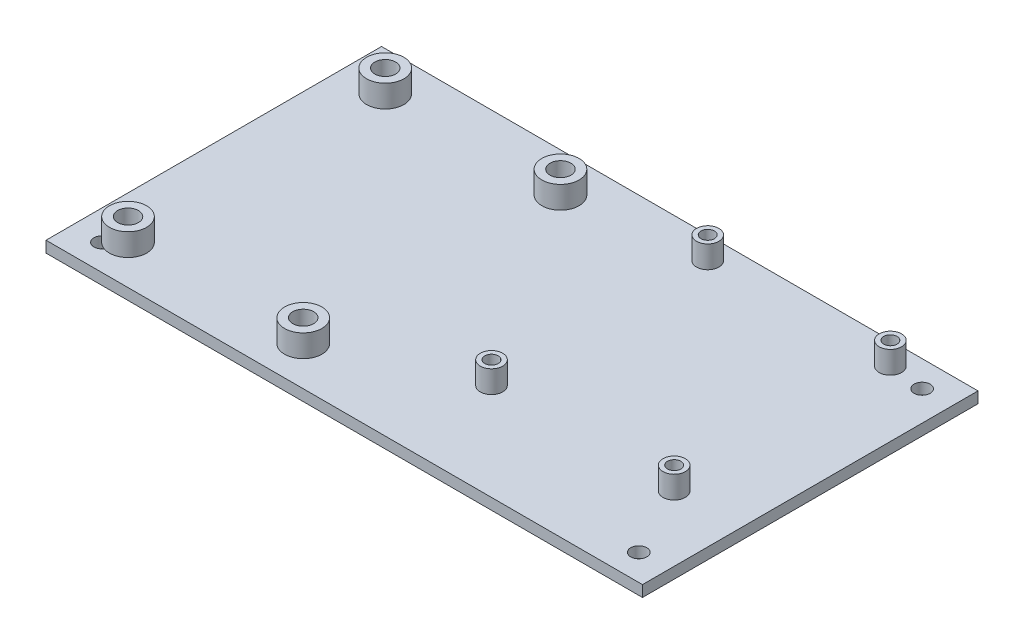
SolidWorks part; units mm, degrees
ref_plane "Front Plane" through (0, 0, 0) normal (0, 0, 1) x (1, 0, 0)
ref_plane "Top Plane" through (0, 0, 0) normal (0, 1, 0) x (1, 0, 0)
ref_plane "Right Plane" through (0, 0, 0) normal (1, 0, 0) x (0, 0, -1)
sketch "SK_Plate" plane through (0, 0, 0) normal (0, 1, 0) x (1, 0, 0)
  line L1 (-80, 45) -> (80, 45)
  line L2 (-80, 45) -> (-80, -45)
  line L3 (-80, -45) -> (80, -45)
  line L4 (80, 45) -> (80, -45)
  dimension "D1" = 90
  dimension "D2" = 160
  dimension "D3" = 45
  dimension "D4" = 80
extrude "EX_Plate" add sketch "SK_Plate" along normal blind 3
ref_plane "PL_Zp3" through (0, 3, 0) normal (0, 1, 0) x (1, 0, 0)
sketch "SK_Standoffs" plane through (0, 3, 0) normal (0, 1, 0) x (1, 0, 0)
  circle A0 centre (62.5, 39) radius 3
  circle A1 centre (13.5, 39) radius 3
  circle A2 centre (62.5, -19) radius 3
  circle A3 centre (13.5, -19) radius 3
  circle A4 centre (-21.5, -34.5) radius 5
  circle A5 centre (-68.5, -34.5) radius 5
  circle A6 centre (-21.5, 34.5) radius 5
  circle A7 centre (-68.5, 34.5) radius 5
  dimension "D3" = 6
  dimension "D6" = 6
  dimension "D9" = 6
  dimension "D12" = 6
  dimension "D15" = 10
  dimension "D18" = 10
  dimension "D21" = 10
  dimension "D24" = 10
  dimension "D1" = 39
  dimension "D2" = 62.5
  dimension "D4" = 39
  dimension "D5" = 13.5
  dimension "D7" = 19
  dimension "D8" = 62.5
  dimension "D10" = 19
  dimension "D11" = 13.5
  dimension "D13" = 34.5
  dimension "D14" = 21.5
  dimension "D16" = 34.5
  dimension "D17" = 68.5
  dimension "D19" = 34.5
  dimension "D20" = 21.5
  dimension "D22" = 34.5
  dimension "D23" = 68.5
extrude "EX_Standoffs" add sketch "SK_Standoffs" along normal blind 6
ref_plane "PL_Zp9" through (0, 9, 0) normal (0, 1, 0) x (1, 0, 0)
sketch "SK_Inserts" plane through (0, 9, 0) normal (0, 1, 0) x (1, 0, 0)
  circle A0 centre (62.5, 39) radius 1.8
  circle A1 centre (13.5, 39) radius 1.8
  circle A2 centre (62.5, -19) radius 1.8
  circle A3 centre (13.5, -19) radius 1.8
  circle A4 centre (-21.5, -34.5) radius 2.8
  circle A5 centre (-68.5, -34.5) radius 2.8
  circle A6 centre (-21.5, 34.5) radius 2.8
  circle A7 centre (-68.5, 34.5) radius 2.8
  dimension "D3" = 3.6
  dimension "D6" = 3.6
  dimension "D9" = 3.6
  dimension "D12" = 3.6
  dimension "D15" = 5.6
  dimension "D18" = 5.6
  dimension "D21" = 5.6
  dimension "D24" = 5.6
  dimension "D1" = 39
  dimension "D2" = 62.5
  dimension "D4" = 39
  dimension "D5" = 13.5
  dimension "D7" = 19
  dimension "D8" = 62.5
  dimension "D10" = 19
  dimension "D11" = 13.5
  dimension "D13" = 34.5
  dimension "D14" = 21.5
  dimension "D16" = 34.5
  dimension "D17" = 68.5
  dimension "D19" = 34.5
  dimension "D20" = 21.5
  dimension "D22" = 34.5
  dimension "D23" = 68.5
extrude "CUT_Inserts" cut sketch "SK_Inserts" against normal blind 6
sketch "SK_PanHoles" plane through (0, 0, 0) normal (0, 1, 0) x (1, 0, 0)
  circle A0 centre (72, -38) radius 2.15
  circle A1 centre (-72, -38) radius 2.15
  circle A2 centre (72, 38) radius 2.15
  circle A3 centre (-72, 38) radius 2.15
  dimension "D3" = 4.3
  dimension "D6" = 4.3
  dimension "D9" = 4.3
  dimension "D12" = 4.3
  dimension "D1" = 38
  dimension "D2" = 72
  dimension "D4" = 38
  dimension "D5" = 72
  dimension "D7" = 38
  dimension "D8" = 72
  dimension "D10" = 38
  dimension "D11" = 72
extrude "CUT_PanHoles" cut sketch "SK_PanHoles" along normal blind 3
ref_axis "AX_X" through (0, 0, -49.5) along (0, 0, 1)
ref_axis "AX_Y" through (88, 0, 0) along (-1, 0, 0)
ref_axis "AX_Z" through (0, 9.45, 0) along (0, -1, 0)
sketch "SK_F_IF_Pi" plane through (0, 9, 0) normal (0, 1, 0) x (1, 0, 0)
  point P0 (38, 0)
  dimension "D1" = 38
sketch "SK_F_IF_ESP32" plane through (0, 9, 0) normal (0, 1, 0) x (1, 0, 0)
  point P0 (-45, 0)
  dimension "D1" = 45
equation "\"BODY_L\"= 420"
equation "\"BODY_W\"= 340"
equation "\"FLOOR_Z\"= 35"
equation "\"DECK_Z\"= 180"
equation "\"DECK_T\"= 2"
equation "\"GRID\"= 20"
equation "\"PROFILE\"= 20"
equation "\"SM_T\"= 1.5"
equation "\"PAN_T\"= 1.5"
equation "\"PAN_TOP\"= \"FLOOR_Z\" + \"PAN_T\""
equation "\"RAIL_Y\"= 140"
equation "\"RAIL_X\"= \"BODY_L\" / 2 - \"PROFILE\" / 2 - 2"
equation "\"BOTRING_Z\"= \"PAN_TOP\" + \"PROFILE\" / 2"
equation "\"TOPRING_Z\"= \"DECK_Z\" - \"DECK_T\" - \"PROFILE\" / 2"
equation "\"DRAWER_Z\"= 93"
equation "\"MIDX_Z\"= \"DRAWER_Z\" - \"SM_T\" - \"PROFILE\" / 2"
equation "\"SKIN_Y\"= \"RAIL_Y\" + \"PROFILE\" / 2"
equation "\"SKIN_T\"= 2"
equation "\"WHEEL_D\"= 144"
equation "\"WHEEL_W\"= 52"
equation "\"TRACK\"= 365"
equation "\"AXLE_Z\"= \"WHEEL_D\" / 2"
equation "\"WHEEL_WEB_OFF\"= 6"
equation "\"HUB_T\"= 8"
equation "\"BUSHING_L\"= 6"
equation "\"HUB_GAP\"= 1"
equation "\"MOTOR_UP\"= 7"
equation "\"MOTOR_FACE_Y\"= \"TRACK\" / 2 + \"WHEEL_WEB_OFF\" - (\"BUSHING_L\" + \"HUB_GAP\" + \"HUB_T\")"
equation "\"MOTOR_AXIS_Z\"= \"AXLE_Z\" + \"MOTOR_UP\""
equation "\"CASTER_D\"= 50"
equation "\"CASTER_X\"= 150"
equation "\"CASTER_H\"= 68"
equation "\"POST_X\"= -40"
equation "\"POST_DY\"= 120"
equation "\"POST_SIZE\"= 20"
equation "\"POST_TOP\"= 400"
equation "\"BRACE_Z\"= 335"
equation "\"STRUT_X0\"= -140"
equation "\"HEAD_X0\"= -110"
equation "\"HEAD_X1\"= 12"
equation "\"BEZEL_T\"= 3"
equation "\"WEDGE_MID\"= 7.7"
equation "\"OAK_D\"= 22.9"
equation "\"HEAD_W\"= 210"
equation "\"HEAD_Z0\"= \"POST_TOP\""
equation "\"HEAD_TOP\"= 525"
equation "\"HEAD_TOP_X\"= -20"
equation "\"SCREEN_ANG\"= 35"
equation "\"LENS_X\"= 45.6"
equation "\"LENS_Z\"= 450"
equation "\"OAK_TILT\"= 5"
equation "\"OAK_VFOV_DEPTH\"= 79.5"
equation "\"OAK_VFOV_RGB\"= 72"
equation "\"LIDAR_X\"= 110"
equation "\"SCAN_Z\"= 260"
equation "\"STRUT_Z\"= \"SCAN_Z\" - 20"
equation "\"LIDAR_SCAN_H\"= 27.2"
equation "\"LIDAR_MOUNT_Z\"= \"SCAN_Z\" - \"LIDAR_SCAN_H\""
equation "\"ESTOP_X\"= -172.5"
equation "\"ESTOP_Y\"= -127.5"
equation "\"ESTOP_TOP\"= 225"
equation "\"BUMPER_T\"= 15"
equation "\"BUMPER_Z0\"= 40"
equation "\"BUMPER_Z1\"= 130"
equation "\"CLIFF_X\"= 218"
equation "\"CLIFF_Y\"= 105"
equation "\"CLIFF_Z\"= 72"
equation "\"CLIFF_ANG\"= 50"
equation "\"CONTACT_X\"= 216"
equation "\"CONTACT_Y\"= 64"
equation "\"CONTACT_Z\"= 30"
equation "\"DOCK_TAG_DIST\"= 250"
equation "\"DOCK_TAG_SIZE\"= 80"
equation "\"DOCK_TAG_Z\"= 400"
equation "\"BAT_L\"= 240"
equation "\"BAT_W\"= 90"
equation "\"BAT_H\"= 58"
equation "\"BAT_Z\"= \"DRAWER_Z\" + \"SM_T\""
equation "\"BAT_X\"= 0"
equation "\"PCB_L\"= 95"
equation "\"PCB_W\"= 120"
equation "\"PCB_H\"= 40"
equation "\"PCB_X\"= 62.5"
equation "\"DRV_X\"= 85"
equation "\"DRV_Y\"= 100"
equation "\"DRV_S\"= 50"
equation "\"COMPUTE_X\"= -65"
equation "\"COMPUTE_L\"= 90"
equation "\"COMPUTE_W\"= 160"
equation "\"D1@SK_Plate\" = \"COMPUTE_L\""
equation "\"D2@SK_Plate\" = \"COMPUTE_W\""
equation "\"D3@SK_Plate\" = (\"COMPUTE_L\") / 2"
equation "\"D4@SK_Plate\" = (\"COMPUTE_W\") / 2"
